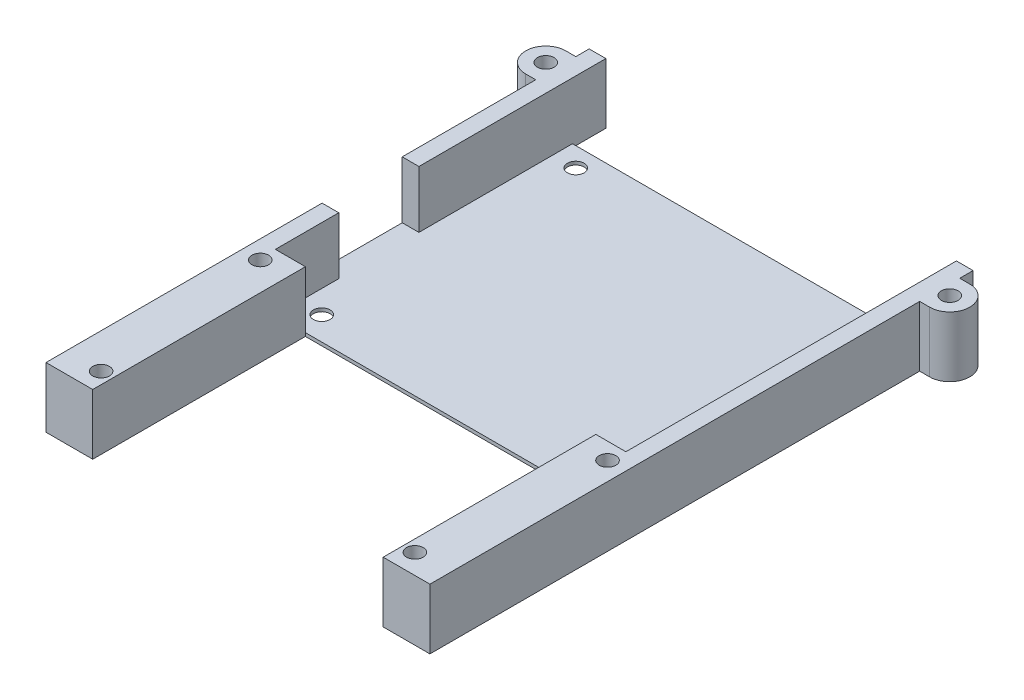
SolidWorks part; units mm, degrees
ref_plane "Front Plane" through (0, 0, 0) normal (0, 0, 1) x (1, 0, 0)
ref_plane "Top Plane" through (0, 0, 0) normal (0, 1, 0) x (1, 0, 0)
ref_plane "Right Plane" through (0, 0, 0) normal (1, 0, 0) x (0, 0, -1)
sketch "Sketch1" plane through (0, 0, 0) normal (0, 1, 0) x (1, 0, 0)
  line L0 (0, 0) -> (0, 76.35) construction
  line L1 (-28.75, 76.35) -> (28.75, 76.35)
  line L2 (28.75, 76.35) -> (28.75, 0)
  line L3 (28.75, 0) -> (21.75, 0)
  line L4 (21.75, 0) -> (21.75, 31.85)
  line L5 (21.75, 31.85) -> (-21.75, 31.85)
  line L6 (-21.75, 31.85) -> (-21.75, 0)
  line L7 (-21.75, 0) -> (-28.75, 0)
  line L8 (-28.75, 0) -> (-28.75, 76.35)
  line L9 (-26.25, 76.35) -> (-26.25, 31.85)
  line L14 (-26.25, 31.85) -> (-21.75, 31.85)
  line L15 (26.25, 76.35) -> (26.25, 31.85)
  line L16 (26.25, 31.85) -> (21.75, 31.85)
  line L17 (28.75, 79.35) -> (30.25, 79.35)
  line L18 (-28.75, 41.35) -> (-26.25, 41.35)
  line L19 (-28.75, 41.35) -> (-28.75, 53.35)
  line L20 (-28.75, 53.35) -> (-26.25, 53.35)
  line L21 (-26.25, 41.35) -> (-26.25, 53.35)
  line L22 (30.25, 73.35) -> (28.75, 73.35)
  line L23 (-30.25, 73.35) -> (-28.75, 73.35)
  line L24 (-28.75, 79.35) -> (-30.25, 79.35)
  line L25 (26.25, 76.35) -> (26.25, 81.35)
  line L26 (26.25, 81.35) -> (28.75, 81.35)
  line L27 (28.75, 81.35) -> (28.75, 76.35)
  line L28 (-28.75, 76.35) -> (-28.75, 81.35)
  line L29 (-28.75, 81.35) -> (-26.25, 81.35)
  line L30 (-26.25, 81.35) -> (-26.25, 76.35)
  arc A0 (30.25, 73.35) -> (30.25, 79.35) centre (30.25, 76.35) ccw
  arc A1 (-30.25, 73.35) -> (-30.25, 79.35) centre (-30.25, 76.35) cw
  point P10 (0, 76.35)
  point P16 (-27.5, 41.35)
  point P17 (-22.85, 73.45)
  point P18 (22.85, 73.45)
  point P23 (22.85, 35.4)
  point P24 (-22.85, 35.4)
  point P25 (23.5, 3)
  point P26 (26, 29.35)
  point P27 (-26, 29.35)
  point P28 (-23.5, 3)
  point P40 (30.25, 76.35)
  point P41 (-30.25, 76.35)
  dimension "D16" = 3
  dimension "D1" = 2.5
  dimension "D2" = 7
  dimension "D3" = 43.5
  dimension "D4" = 31.85
  dimension "D5" = 44.5
  dimension "D6" = 23
  dimension "D7" = 12
  dimension "D8" = 22.85
  dimension "D9" = 38.05
  dimension "D10" = 2.9
  dimension "D11" = 47
  dimension "D12" = 52
  dimension "D13" = 47
  dimension "D14" = 3
  dimension "D15" = 1.5
  dimension "D17" = 2
  dimension "D18" = 5
extrude "Boss-Extrude1" add sketch "Sketch1" along normal blind 0.5 contours L5 L0 L1 L9 L14 | L0 L5 L16 L15 L1 | L20 L8 L18 L9 region at (-13.125, 0, -54.1) region at (13.125, 0, -54.1) region at (-27.5, 0, -47.35)
extrude "Boss-Extrude2" add sketch "Sketch1<3>" along normal blind 9.05 contours L18 L8 L7 L6 L14 L9 | L8 L20 L9 L1 | L15 L16 L4 L3 L2 L1 | A1 L23 L8 L24 | L22 A0 L17 L2 | L27 L26 L25 L1 | L30 L29 L28 L1 region at (-27.5, 0, -78.85) region at (-27.5, 0, -64.85) region at (-30.7362, 0, -76.35) region at (27.5, 0, -78.85) region at (25.999, 0, -28.6329) region at (30.7362, 0, -76.35) region at (-25.4666, 0, -17.9154)
sketch "Sketch1<3>" plane through (0, 0, 0) normal (0, 1, 0) x (1, 0, 0) same geometry as "Sketch1"
hole_wizard "Ø2.5 (2.5) Diameter Hole1" positions "Sketch4" profile "Sketch5" hole size "Ø2.5" standard "ANSI Metric"
sketch "Sketch4" plane through (0, 0, 0) normal (0, -1, 0) x (-1, 0, 0)
  point P0 (-22.85, 73.45)
  point P3 (22.85, 73.45)
  point P6 (26, 29.35)
  point P9 (22.85, 35.4)
  point P12 (-22.85, 35.4)
  point P15 (-26, 29.35)
  point P18 (-23.5, 3)
  point P21 (23.5, 3)
  point P24 (-30.25, 76.35)
  point P27 (30.25, 76.35)
sketch "Sketch5" plane through (22.85, 0, -73.45) normal (1, 0, 0) x (0, 0, -1)
  line L0 (0, 0) -> (0, 12.7511)
  line L1 (0, 12.7511) -> (1.25, 12)
  line L2 (1.25, 12) -> (1.25, 0)
  line L5 (1.25, 0) -> (0, 0)
  line L10 (0, 12.7511) -> (-1.25, 12) construction
  line L11 (0, -6.35) -> (0, 107.95) construction
  dimension "Hole Dia." = 2.5
  dimension "Hole Depth" = 12
  dimension "Drill Angle" = 118
